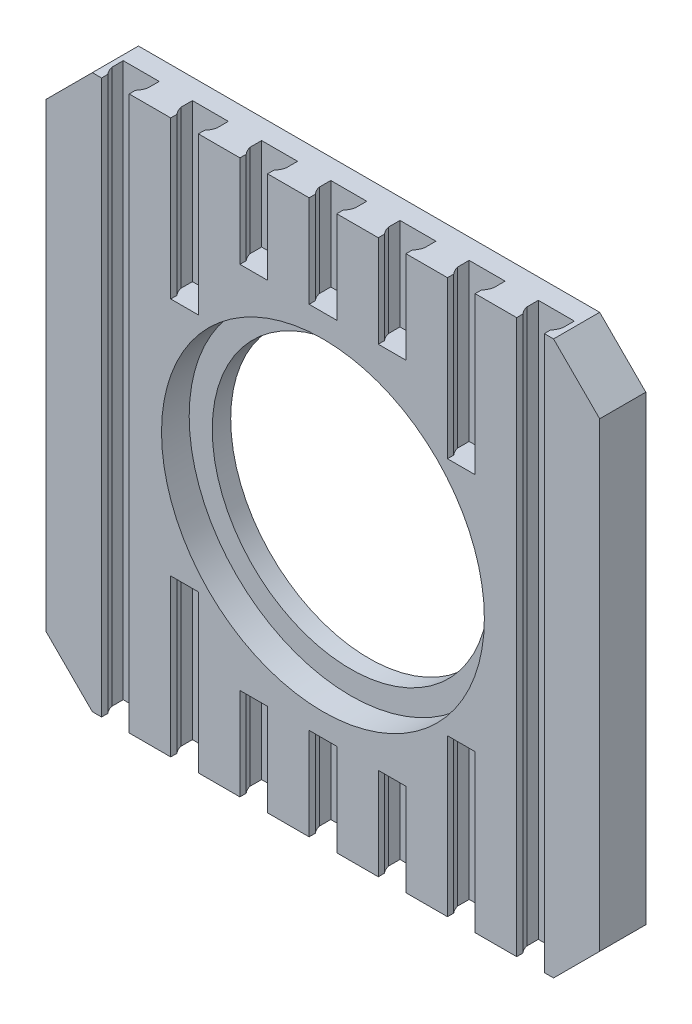
SolidWorks part; units mm, degrees
ref_plane "前视基准面" through (0, 0, 0) normal (0, 0, 1) x (1, 0, 0)
ref_plane "上视基准面" through (0, 0, 0) normal (0, 1, 0) x (1, 0, 0)
ref_plane "右视基准面" through (0, 0, 0) normal (1, 0, 0) x (0, 0, -1)
sketch "草图1" plane through (0, 0, 0) normal (0, 0, 1) x (1, 0, 0)
  circle A0 centre (0, 0) radius 45
extrude "凸台-拉伸1" add sketch "草图1" against normal blind 5
sketch "草图2" plane through (0, 0, 0) normal (0, 0, 1) x (1, 0, 0)
  line L1 (-30, 30) -> (30, 30)
  line L2 (-30, 30) -> (-30, -30)
  line L3 (-30, -30) -> (30, -30)
  line L4 (30, 30) -> (30, -30)
extrude "凸台-拉伸2" add sketch "草图2" along normal blind 5
sketch "草图3" plane through (0, -30, 0) normal (0, -1, 0) x (1, 0, 0)
  line L0 (-30, 5) -> (30, 5) construction
  line L1 (-1.5, 5) -> (1.5, 5)
  line L2 (-1.5, 5) -> (-1.5, 4.3229)
  line L3 (6, 5) -> (6, 4.3229)
  line L4 (1.5, 5) -> (1.5, 4.3229)
  line L5 (-1.95, 2.2) -> (1.95, 2.2)
  line L6 (-1.95, 2.2) -> (-1.95, 3.4444)
  line L7 (1.95, 2.2) -> (1.95, 3.4444)
  line L8 (9.45, 2.2) -> (9.45, 3.4444)
  line L9 (9, 5) -> (9, 4.3229)
  line L10 (6, 5) -> (9, 5)
  line L11 (5.55, 2.2) -> (9.45, 2.2)
  line L12 (5.55, 2.2) -> (5.55, 3.4444)
  line L13 (-9, 5) -> (-9, 4.3229)
  line L14 (-5.55, 2.2) -> (-5.55, 3.4444)
  line L15 (-6, 5) -> (-6, 4.3229)
  line L16 (-9, 5) -> (-6, 5)
  line L17 (-9.45, 2.2) -> (-5.55, 2.2)
  line L18 (-9.45, 2.2) -> (-9.45, 3.4444)
  arc A0 (6, 4.3229) -> (5.55, 3.4444) centre (7.5, 3) ccw
  arc A1 (-1.5, 4.3229) -> (-1.95, 3.4444) centre (0, 3) ccw
  arc A2 (1.95, 3.4444) -> (1.5, 4.3229) centre (0, 3) ccw
  arc A3 (9.45, 3.4444) -> (9, 4.3229) centre (7.5, 3) ccw
  arc A4 (-9, 4.3229) -> (-9.45, 3.4444) centre (-7.5, 3) ccw
  arc A5 (-5.55, 3.4444) -> (-6, 4.3229) centre (-7.5, 3) ccw
extrude "切除-拉伸1" cut sketch "草图3" against normal blind 10
extrude "切除-拉伸2" cut sketch "草图3<2>" along normal blind 10 from offset 60 offset against normal yes
sketch "草图3<2>" plane through (0, -30, 0) normal (0, -1, 0) x (1, 0, 0) same geometry as "草图3"
sketch "草图4" plane through (0, -30, 0) normal (0, -1, 0) x (1, 0, 0)
  line L0 (-16.5, 5) -> (-13.5, 5)
  line L3 (-16.5, 5) -> (-16.5, 4.3229)
  line L7 (-16.95, 2.2) -> (-13.05, 2.2)
  line L9 (-13.5, 5) -> (-13.5, 4.3229)
  line L10 (-16.95, 2.2) -> (-16.95, 3.4444)
  line L11 (-13.05, 2.2) -> (-13.05, 3.4444)
  line L12 (13.5, 5) -> (16.5, 5)
  line L13 (13.5, 5) -> (13.5, 4.3229)
  line L14 (13.05, 2.2) -> (16.95, 2.2)
  line L15 (16.5, 5) -> (16.5, 4.3229)
  line L16 (13.05, 2.2) -> (13.05, 3.4444)
  line L17 (16.95, 2.2) -> (16.95, 3.4444)
  arc A2 (-16.5, 4.3229) -> (-16.95, 3.4444) centre (-15, 3) ccw
  arc A3 (-13.05, 3.4444) -> (-13.5, 4.3229) centre (-15, 3) ccw
  arc A4 (13.5, 4.3229) -> (13.05, 3.4444) centre (15, 3) ccw
  arc A5 (16.95, 3.4444) -> (16.5, 4.3229) centre (15, 3) ccw
extrude "切除-拉伸3" cut sketch "草图4" against normal blind 17
extrude "切除-拉伸4" cut sketch "草图4<2>" along normal blind 17 from offset 60 offset against normal yes
sketch "草图4<2>" plane through (0, -30, 0) normal (0, -1, 0) x (1, 0, 0) same geometry as "草图4"
sketch "草图5" plane through (0, -30, 0) normal (0, -1, 0) x (1, 0, 0)
  line L0 (-21, 5) -> (-21, 4.3229)
  line L3 (-24, 5) -> (-21, 5)
  line L7 (-24.45, 2.2) -> (-20.55, 2.2)
  line L9 (-20.55, 2.2) -> (-20.55, 3.4444)
  line L10 (-24.45, 2.2) -> (-24.45, 3.4444)
  line L11 (-24, 5) -> (-24, 4.3229)
  line L12 (24, 5) -> (24, 4.3229)
  line L13 (21, 5) -> (24, 5)
  line L14 (20.55, 2.2) -> (24.45, 2.2)
  line L15 (24.45, 2.2) -> (24.45, 3.4444)
  line L16 (20.55, 2.2) -> (20.55, 3.4444)
  line L17 (21, 5) -> (21, 4.3229)
  arc A2 (-24, 4.3229) -> (-24.45, 3.4444) centre (-22.5, 3) ccw
  arc A3 (-20.55, 3.4444) -> (-21, 4.3229) centre (-22.5, 3) ccw
  arc A4 (21, 4.3229) -> (20.55, 3.4444) centre (22.5, 3) ccw
  arc A5 (24.45, 3.4444) -> (24, 4.3229) centre (22.5, 3) ccw
extrude "切除-拉伸5" cut sketch "草图5" against normal up to next
chamfer "倒角1" distance 5 angle 45 4 edges at (-30, 30, 2.5) (30, 30, 2.5) (30, -30, 2.5) (-30, -30, 2.5)
sketch "草图6" plane through (0, 0, 5) normal (0, 0, 1) x (1, 0, 0)
  circle A0 centre (0, 0) radius 17.5
extrude "切除-拉伸6" cut sketch "草图6" against normal blind 3
sketch "草图7" plane through (0, 0, 2) normal (0, 0, 1) x (1, 0, 0)
  circle A0 centre (0, 0) radius 15
extrude "切除-拉伸7" cut sketch "草图7" against normal through all
sketch "草图8" plane through (0, 0, 0) normal (0, 0, 1) x (1, 0, 0)
  circle A0 centre (0, 0) radius 45
extrude "切除-拉伸9" cut sketch "草图8" against normal blind 10
